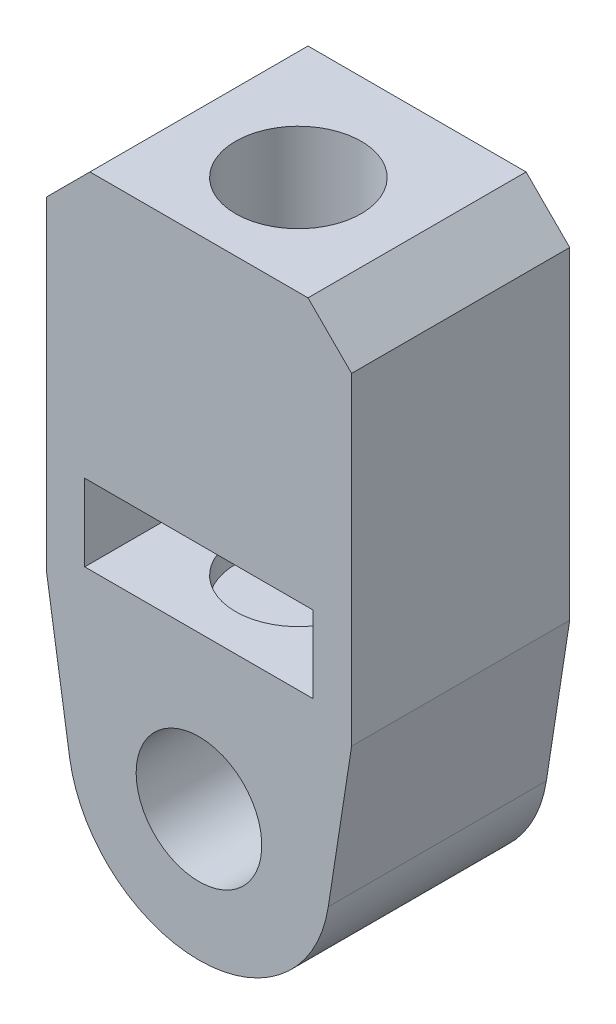
SolidWorks part; units mm, degrees
ref_plane "Front Plane" through (0, 0, 0) normal (0, 0, 1) x (1, 0, 0)
ref_plane "Top Plane" through (0, 0, 0) normal (0, 1, 0) x (1, 0, 0)
ref_plane "Right Plane" through (0, 0, 0) normal (1, 0, 0) x (0, 0, -1)
sketch "Sketch1" plane through (0, 0, 0) normal (0, 0, 1) x (1, 0, 0)
  line L0 (-5.5562, 4.7625) -> (-5.5562, 18.0975)
  line L1 (-5.5562, 18.0975) -> (5.5562, 18.0975)
  line L2 (5.5562, 18.0975) -> (5.5562, 4.7625)
  line L3 (-5.5562, 4.7625) -> (-4.7065, -0.7284)
  line L4 (4.7065, -0.7284) -> (5.5562, 4.7625)
  circle A1 centre (0, 0) radius 2.286
  arc A2 (-4.7065, -0.7284) -> (4.7065, -0.7284) centre (0, 0) ccw
  point P10 (0, 18.0975)
  dimension "D1" = 9.525
  dimension "D2" = 4.572
  dimension "D3" = 13.335
  dimension "D4" = 11.1125
  dimension "D5" = 4.7625
extrude "Boss-Extrude1" add sketch "Sketch1" along normal up to surface (7.9375 mm away)
sketch "Sketch2" plane through (0, 18.0975, 0) normal (0, 1, 0) x (1, 0, 0)
  circle A1 centre (0, -4.3188) radius 2.286
  circle A2 centre (0, -4.3188) radius 1.7525 construction
  dimension "D1" = 4.572
extrude "Cut-Extrude1" cut sketch "Sketch2" against normal offset from surface (13.335 mm away) 4.7625 up to plane "Top Plane"
sketch "Sketch3" plane through (0, 4.7625, 0) normal (0, 1, 0) x (1, 0, 0)
  line L11 (5.5562, -7.9375) -> (-5.5562, -7.9375) construction
  line L12 (-1.9064, -1.0168) -> (-4.1565, -4.9141)
  line L16 (4.1565, -4.9141) -> (1.9064, -1.0168)
  line L17 (1.9064, -1.0168) -> (-1.9064, -1.0168)
  line L18 (-4.1565, -4.9141) -> (-4.1565, -7.9375)
  line L19 (-4.1565, -7.9375) -> (4.1565, -7.9375)
  line L20 (4.1565, -7.9375) -> (4.1565, -4.9141)
  line L22 (-1.9064, -7.6208) -> (0, -7.6208) [skipped]
  line L23 (-3.8128, -4.3188) -> (-2.8596, -5.9698) [skipped]
  line L24 (2.1818, -7.1438) -> (2.8596, -5.9698) [skipped]
  circle A0 centre (0, -4.3188) radius 3.302 construction
  dimension "D1" = 6.604
extrude "Cut-Extrude2" cut sketch "Sketch3" along normal blind 2.794 from offset 0.7937
chamfer "Chamfer1" distance 1.5875 angle 45 2 edges at (5.5562, 18.0975, 3.9687) (-5.5562, 18.0975, 3.9687)
